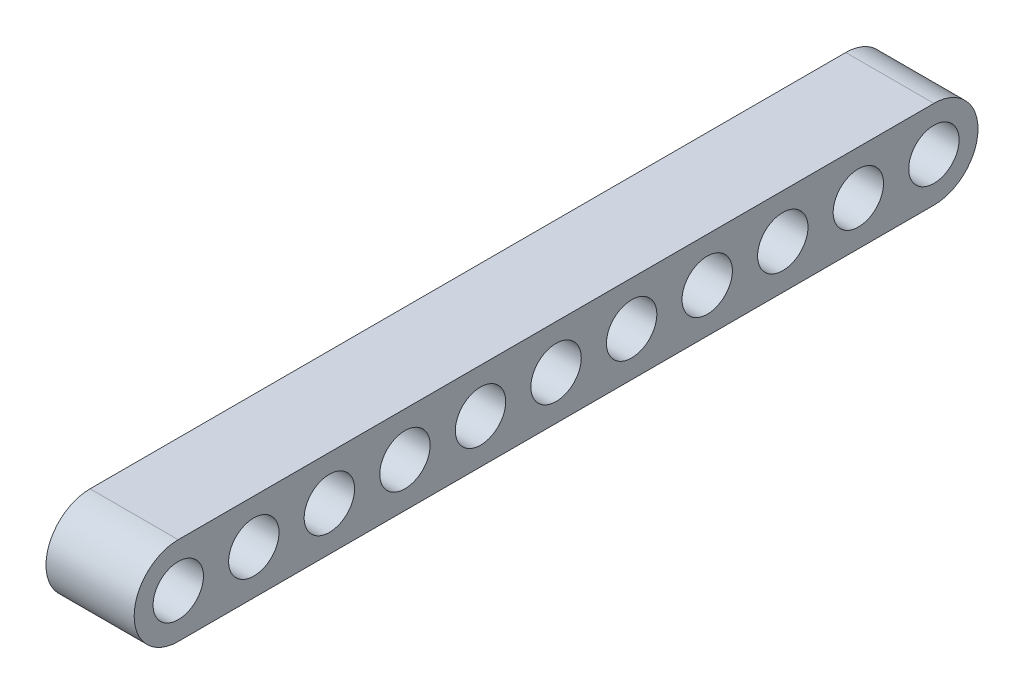
SolidWorks part; units mm, degrees
ref_plane "Front Plane" through (0, 0, 0) normal (0, 0, 1) x (1, 0, 0)
ref_plane "Top Plane" through (0, 0, 0) normal (0, 1, 0) x (1, 0, 0)
ref_plane "Right Plane" through (0, 0, 0) normal (1, 0, 0) x (0, 0, -1)
sketch "Sketch1" plane through (0, 0, 0) normal (1, 0, 0) x (0, 0, -1)
  line L0 (0, 0) -> (-600, 0) construction
  line L1 (0, -35) -> (-600, -35)
  line L2 (0, 35) -> (-600, 35)
  arc A0 (0, -35) -> (0, 35) centre (0, 0) ccw
  arc A1 (-600, 35) -> (-600, -35) centre (-600, 0) ccw
  circle A2 centre (-600, 0) radius 20
  circle A3 centre (-540, 0) radius 20
  circle A4 centre (-480, 0) radius 20
  circle A5 centre (-420, 0) radius 20
  circle A6 centre (-360, 0) radius 20
  circle A7 centre (-300, 0) radius 20
  circle A8 centre (-240, 0) radius 20
  circle A9 centre (-180, 0) radius 20
  circle A10 centre (-120, 0) radius 20
  circle A11 centre (-60, 0) radius 20
  circle A12 centre (0, 0) radius 20
  point P3 (-300, 0)
  dimension "D3" = 40
  dimension "D1" = 600
  dimension "D2" = 70
  dimension "D4" = 11
extrude "Boss-Extrude1" add sketch "Sketch1" along normal blind 70
